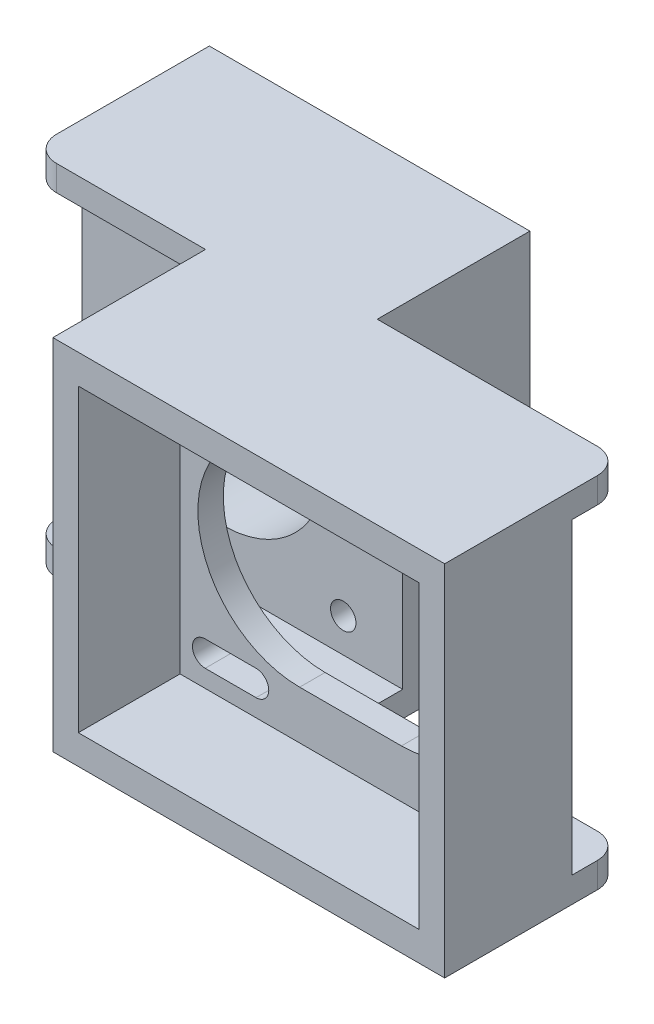
SolidWorks part; units mm, degrees
ref_plane "Front Plane" through (0, 0, 0) normal (0, 0, 1) x (1, 0, 0)
ref_plane "Top Plane" through (0, 0, 0) normal (0, 1, 0) x (1, 0, 0)
ref_plane "Right Plane" through (0, 0, 0) normal (1, 0, 0) x (0, 0, -1)
sketch "Sketch1" plane through (0, 0, 0) normal (0, 1, 0) x (1, 0, 0)
  line L0 (-24.125, 32.5) -> (-24.125, -12.5) construction
  line L5 (-59.375, 12.5) -> (59.375, 12.5)
  line L6 (-59.375, 12.5) -> (-59.375, -12.5)
  line L7 (-59.375, -12.5) -> (59.375, -12.5)
  line L8 (59.375, 12.5) -> (59.375, -12.5)
  line L9 (-59.375, 12.5) -> (59.375, -12.5) construction
  line L10 (-59.375, -12.5) -> (59.375, 12.5) construction
  line L15 (-59.375, 12.5) -> (11.125, 12.5)
  line L16 (-59.375, 12.5) -> (-59.375, 32.5)
  line L17 (-59.375, 32.5) -> (11.125, 32.5)
  line L18 (11.125, 12.5) -> (11.125, 32.5)
  line L19 (59.375, -12.5) -> (-17.625, -12.5)
  line L20 (59.375, -12.5) -> (59.375, -32.5)
  line L21 (59.375, -32.5) -> (-17.625, -32.5)
  line L22 (-17.625, -12.5) -> (-17.625, -32.5)
  line L23 (20.875, -32.5) -> (20.875, 12.5) construction
  point P0 (0, 0)
  dimension "D4" = 20
  dimension "D5" = 20
  dimension "D1" = 45
  dimension "D2" = 25
  dimension "D3" = 70.5
  dimension "D6" = 77
extrude "Boss-Extrude1" add sketch "Sketch1" along normal blind 70.5 contours L7 L22 L21 L20 | L8 L5 L6 L7 | L5 L18 L17 L16 region at (-24.125, 0, -22.5) region at (0, 0, 0) region at (20.875, 0, 22.5)
sketch "Sketch6" plane through (59.375, 0, 0) normal (1, 0, 0) x (0, 0, -1)
  line L0 (7.5, 65.5) -> (7.5, 5)
  line L1 (12.5, 70.5) -> (-12.5, 70.5)
  line L2 (12.5, 70.5) -> (12.5, 0)
  line L3 (12.5, 0) -> (-12.5, 0)
  line L4 (-12.5, 70.5) -> (-12.5, 0)
  line L5 (7.5, 5) -> (-7.5, 5)
  line L6 (-7.5, 65.5) -> (-7.5, 5)
  line L7 (7.5, 65.5) -> (-7.5, 65.5)
  dimension "D1" = 5
extrude "Cut-Extrude2" cut sketch "Sketch6" against normal up to surface (48.25 mm away) contours L0 L5 L6 L7 up to face at (11.125, 35.25, -22.5)
sketch "Sketch7" plane through (0, 0, 32.5) normal (0, 0, 1) x (1, 0, 0)
  line L0 (-17.625, 35.25) -> (59.375, 35.25) construction
  line L1 (-17.625, 70.5) -> (-17.625, 0) construction
  line L2 (59.375, 70.5) -> (59.375, 0) construction
  line L4 (-12.625, 64.75) -> (54.375, 64.75)
  line L5 (-12.625, 64.75) -> (-12.625, 5.75)
  line L6 (-12.625, 5.75) -> (54.375, 5.75)
  line L7 (54.375, 64.75) -> (54.375, 5.75)
  line L8 (-12.625, 64.75) -> (54.375, 5.75) construction
  line L9 (-12.625, 5.75) -> (54.375, 64.75) construction
  point P6 (20.875, 35.25)
  dimension "D1" = 67
  dimension "D2" = 59
extrude "Cut-Extrude3" cut sketch "Sketch7" against normal blind 20 contours L5 L4 L7 L6
sketch "Sketch8" plane through (0, 0, 12.5) normal (0, 0, 1) x (1, 0, 0)
  line L0 (-12.625, 35.25) -> (54.375, 35.25) construction
  line L1 (-12.625, 64.75) -> (54.375, 64.75) construction
  line L3 (-12.625, 64.75) -> (-12.625, 5.75) construction
  line L12 (54.375, 64.75) -> (54.375, 5.75) construction
  line L18 (10.875, 55.25) -> (30.875, 55.25)
  line L20 (10.875, 15.25) -> (30.875, 15.25)
  line L26 (10.875, 55.25) -> (30.875, 15.25) construction
  line L27 (10.875, 15.25) -> (30.875, 55.25) construction
  line L41 (20.875, 64.75) -> (20.875, 5.75) construction
  line L42 (-12.625, 5.75) -> (54.375, 5.75) construction
  line L52 (-7.695, 58.82) -> (2.305, 58.82) construction
  line L53 (-7.695, 61.32) -> (2.305, 61.32)
  line L54 (-7.695, 56.32) -> (2.305, 56.32)
  line L55 (-12.625, 64.75) -> (-12.625, 5.75) construction
  line L56 (49.445, 58.82) -> (39.445, 58.82) construction
  line L57 (49.445, 61.32) -> (39.445, 61.32)
  line L58 (49.445, 56.32) -> (39.445, 56.32)
  line L59 (-7.695, 11.68) -> (2.305, 11.68) construction
  line L60 (-7.695, 9.18) -> (2.305, 9.18)
  line L61 (-7.695, 14.18) -> (2.305, 14.18)
  line L62 (49.445, 11.68) -> (39.445, 11.68) construction
  line L63 (49.445, 9.18) -> (39.445, 9.18)
  line L64 (49.445, 14.18) -> (39.445, 14.18)
  arc A0 (30.875, 55.25) -> (30.875, 15.25) centre (30.875, 35.25) cw
  arc A2 (10.875, 55.25) -> (10.875, 15.25) centre (10.875, 35.25) ccw
  arc A12 (-7.695, 61.32) -> (-7.695, 56.32) centre (-7.695, 58.82) ccw
  arc A13 (2.305, 56.32) -> (2.305, 61.32) centre (2.305, 58.82) ccw
  arc A14 (49.445, 61.32) -> (49.445, 56.32) centre (49.445, 58.82) cw
  arc A15 (39.445, 56.32) -> (39.445, 61.32) centre (39.445, 58.82) cw
  arc A16 (-7.695, 9.18) -> (-7.695, 14.18) centre (-7.695, 11.68) cw
  arc A17 (2.305, 14.18) -> (2.305, 9.18) centre (2.305, 11.68) cw
  arc A18 (49.445, 9.18) -> (49.445, 14.18) centre (49.445, 11.68) ccw
  arc A19 (39.445, 14.18) -> (39.445, 9.18) centre (39.445, 11.68) ccw
  point P6 (20.875, 35.25)
  point P15 (-2.695, 58.82)
  point P19 (20.875, 35.25)
  point P28 (44.445, 58.82)
  point P39 (-2.695, 11.68)
  point P46 (44.445, 11.68)
  dimension "D1" = 40
  dimension "D4" = 2.5
  dimension "D2" = 20
  dimension "D3" = 10
  dimension "D5" = 9.93
  dimension "D6" = 5.93
extrude "Cut-Extrude4" cut sketch "Sketch8" against normal blind 5 contours L18 A2 L20 A0 | L54 A13 L53 A12 | L57 A15 L58 A14 | L63 A19 L64 A18 | L60 A17 L61 A16 region at (20.875, 35.25, 12.5)
sketch "Sketch9" plane through (59.375, 0, 0) normal (1, 0, 0) x (0, 0, -1)
  line L0 (12.5, 70.5) -> (12.5, 0) construction
  line L1 (12.5, 65.5) -> (7.5, 65.5)
  line L2 (12.5, 65.5) -> (12.5, 5)
  line L3 (12.5, 5) -> (7.5, 5)
  line L4 (7.5, 65.5) -> (7.5, 5)
extrude "Cut-Extrude5" cut sketch "Sketch9" against normal up to surface (48.25 mm away) up to face at (11.125, 35.25, -22.5)
sketch "Sketch10" plane through (-59.375, 0, 0) normal (-1, 0, 0) x (0, 0, 1)
  line L5 (12.5, 0) -> (-32.5, 0) construction
  line L6 (12.5, 70.5) -> (-12.5, 70.5)
  line L7 (12.5, 70.5) -> (12.5, 0)
  line L8 (12.5, 0) -> (-12.5, 0)
  line L13 (-12.5, 70.5) -> (-12.5, 0)
  line L14 (7.5, 65.5) -> (-7.5, 65.5)
  line L15 (-7.5, 65.5) -> (-7.5, 5)
  line L16 (7.5, 5) -> (-7.5, 5)
  line L17 (7.5, 65.5) -> (7.5, 5)
  dimension "D2" = 5
extrude "Cut-Extrude6" cut sketch "Sketch10" against normal up to surface (70.5 mm away) contours L14 L15 L16 L17 up to face at (11.125, 35.25, -8.5)
sketch "Sketch11" plane through (-59.375, 0, 0) normal (-1, 0, 0) x (0, 0, 1)
  line L0 (12.5, 70.5) -> (12.5, 0) construction
  line L1 (12.5, 65.5) -> (7.5, 65.5)
  line L2 (12.5, 65.5) -> (12.5, 5)
  line L3 (12.5, 5) -> (7.5, 5)
  line L4 (7.5, 65.5) -> (7.5, 5)
extrude "Cut-Extrude7" cut sketch "Sketch11" against normal up to surface (41.75 mm away) up to face at (-17.625, 35.25, 22.5)
sketch "Sketch12" plane through (0, 0, -32.5) normal (0, 0, -1) x (-1, 0, 0)
  line L0 (24.125, 70.5) -> (24.125, 0) construction
  line L1 (59.375, 70.5) -> (-11.125, 70.5) construction
  line L2 (59.375, 0) -> (-11.125, 0) construction
  line L4 (-6.125, 65.5) -> (54.375, 65.5)
  line L5 (-6.125, 65.5) -> (-6.125, 5)
  line L6 (-6.125, 5) -> (54.375, 5)
  line L7 (54.375, 65.5) -> (54.375, 5)
  line L8 (-6.125, 65.5) -> (54.375, 5) construction
  line L9 (-6.125, 5) -> (54.375, 65.5) construction
  point P6 (24.125, 35.25)
  dimension "D1" = 60.5
extrude "Cut-Extrude8" cut sketch "Sketch12" against normal blind 15
sketch "Sketch13" plane through (0, 0, -17.5) normal (0, 0, -1) x (-1, 0, 0)
  line L0 (24.125, 65.5) -> (24.125, 5) construction
  line L1 (54.375, 65.5) -> (-6.125, 65.5) construction
  line L2 (-6.125, 5) -> (54.375, 5) construction
  line L3 (54.375, 65.5) -> (-6.125, 65.5) construction
  line L4 (-6.125, 65.5) -> (-6.125, 5) construction
  line L5 (-6.125, 35.25) -> (54.375, 35.25) construction
  line L6 (54.375, 5) -> (54.375, 65.5) construction
  circle A0 centre (24.125, 35.25) radius 20
  circle A1 centre (0.555, 58.82) radius 2.5
  circle A2 centre (47.695, 58.82) radius 2.5
  circle A3 centre (47.695, 11.68) radius 2.5
  circle A4 centre (0.555, 11.68) radius 2.5
  dimension "D1" = 40
  dimension "D2" = 5
  dimension "D3" = 6.68
  dimension "D4" = 6.68
extrude "Cut-Extrude9" cut sketch "Sketch13" against normal blind 20
sketch "Sketch14" plane through (0, 70.5, 0) normal (0, 1, 0) x (1, 0, 0)
  line L0 (11.125, 12.5) -> (59.375, 12.5) construction
  line L1 (59.375, 12.5) -> (11.125, 12.5)
  line L2 (59.375, 12.5) -> (59.375, 2.5)
  line L3 (59.375, 2.5) -> (11.125, 2.5)
  line L4 (11.125, 12.5) -> (11.125, 2.5)
  line L6 (-59.375, -12.5) -> (-17.625, -12.5)
  line L7 (-59.375, -12.5) -> (-59.375, -2.5)
  line L8 (-59.375, -2.5) -> (-17.625, -2.5)
  line L9 (-17.625, -12.5) -> (-17.625, -2.5)
  line L10 (-17.625, -12.5) -> (-59.375, -12.5) construction
  line L11 (-59.375, 32.5) -> (-51.875, 32.5)
  line L12 (-59.375, 32.5) -> (-59.375, -12.5)
  line L13 (-59.375, -12.5) -> (-51.875, -12.5)
  line L14 (-51.875, 32.5) -> (-51.875, -12.5)
  line M9 (59.375, -32.5) -> (59.375, 12.5)
  line M10 (59.375, 12.5) -> (11.125, 12.5)
  line M12 (11.125, 32.5) -> (-59.375, 32.5)
  line M13 (-59.375, 32.5) -> (-59.375, -12.5)
  line M14 (-59.375, -12.5) -> (-17.625, -12.5)
  dimension "D1" = 10
  dimension "D2" = 7.5
extrude "Cut-Extrude10" cut sketch "Sketch14" against normal through all contours L14 L8 M12 M13 | L14 L8 M13 M14 | L8 L14 L6 L9 | L4 L3 M10 M9 region at (35.25, 70.5, -7.5) region at (-55.625, 70.5, 7.5) region at (-34.75, 70.5, 7.5) region at (-55.625, 70.5, -15)
fillet "Fillet2" radius 5 4 edges at (59.375, 2.5, -2.5) (59.375, 68, -2.5) (-51.875, 2.5, 2.5) (-51.875, 68, 2.5)
